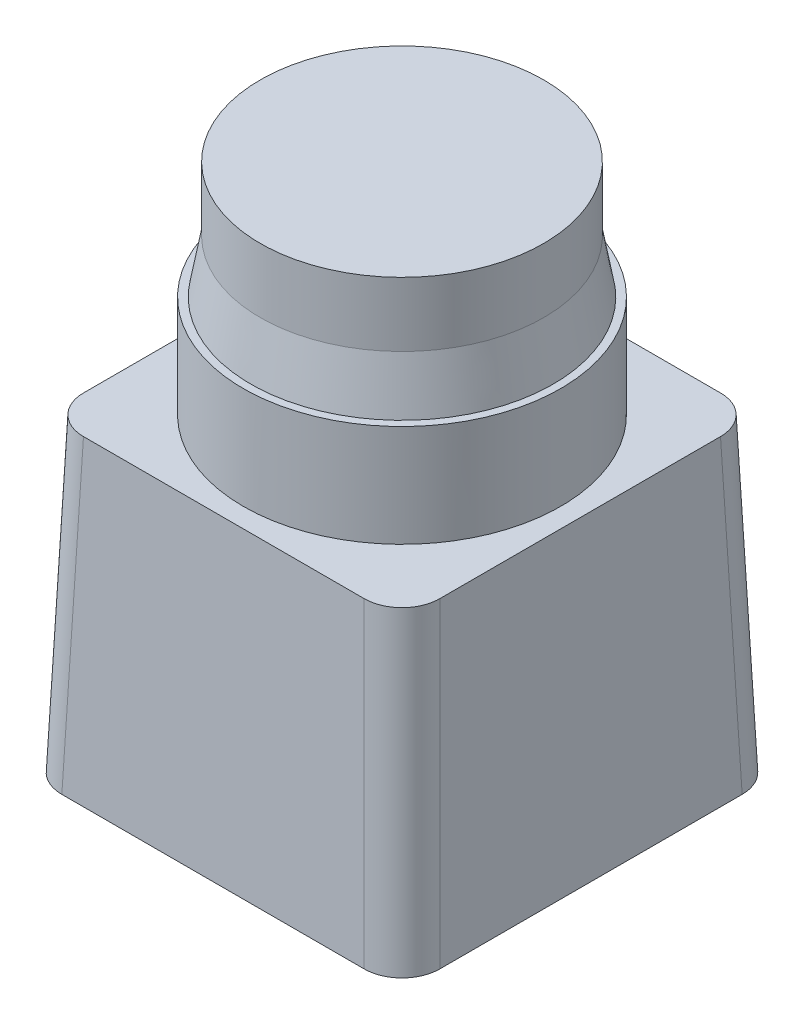
SolidWorks part; units mm, degrees
ref_plane "Plano frontal" through (0, 0, 0) normal (0, 0, 1) x (1, 0, 0)
ref_plane "Plano superior" through (0, 0, 0) normal (0, 1, 0) x (1, 0, 0)
ref_plane "Plano direito" through (0, 0, 0) normal (1, 0, 0) x (0, 0, -1)
sketch "Esboço1" plane through (0, 0, 0) normal (0, 1, 0) x (1, 0, 0)
  line L1 (-25, 25) -> (25, 25)
  line L2 (-25, 25) -> (-25, -25)
  line L3 (-25, -25) -> (25, -25)
  line L4 (25, 25) -> (25, -25)
  line L5 (-25, 25) -> (25, -25) construction
  line L6 (-25, -25) -> (25, 25) construction
  point P0 (0, 0)
  dimension "D1" = 50
  dimension "D2" = 50
extrude "Ressalto-extrusão1" add sketch "Esboço1" along normal blind 41 draft 2
sketch "Esboço2" plane through (0, 0, 0) normal (1, 0, 0) x (0, 0, -1)
  line L0 (0, 41) -> (0, 70) construction
  line L1 (-23.5682, 41) -> (23.5682, 41) construction
  line L2 (0, 70) -> (18.75, 70)
  line L3 (18.75, 70) -> (18.75, 61.5)
  line L4 (18.75, 61.5) -> (20, 54.5)
  line L5 (21, 41) -> (21, 54.5)
  line L6 (20, 54.5) -> (21, 54.5)
  line L7 (0, 41) -> (21, 41)
  line L8 (21, 41) -> (0, 41)
  dimension "D1" = 29
  dimension "D2" = 40
  dimension "D3" = 37.5
  dimension "D4" = 42
  dimension "D5" = 20.5
  dimension "D6" = 13.5
revolve "Revolução1" add sketch "Esboço2" angle 360 about L0 region at (0, 55.1032, -10.0004)
fillet "Filete1" radius 5 4 edges at (-24.2841, 20.5, 24.2841) (-24.2841, 20.5, -24.2841) (24.2841, 20.5, 24.2841) (24.2841, 20.5, -24.2841)
sketch "Esboço3" plane through (0, 0, 0) normal (0, -1, 0) x (-1, 0, 0)
  line L0 (-20, -19.375) -> (-25, -19.375) construction
  line L1 (-25, -20.003) -> (-25, 20.003) construction
  line L2 (20, 20.625) -> (25, 20.625) construction
  line L3 (25, 20.003) -> (25, -20.003) construction
  line L4 (-20, -20.625) -> (-20, -25) construction
  line L5 (20.003, -25) -> (-20.003, -25) construction
  line L6 (20, 20.625) -> (20, 25) construction
  line L7 (-20.003, 25) -> (20.003, 25) construction
  circle A0 centre (20, 20.625) radius 1.25
  circle A1 centre (-20, -19.375) radius 1.25
  dimension "D1" = 2.5
  dimension "D2" = 2.5
  dimension "D3" = 40
  dimension "D4" = 40
extrude "Corte-extrusão1" cut sketch "Esboço3" against normal blind 6
cosmetic thread "Representação de rosca1" parameters "D1"=5, "D2"=3
cosmetic thread "Representação de rosca2" parameters "D1"=5, "D2"=3
